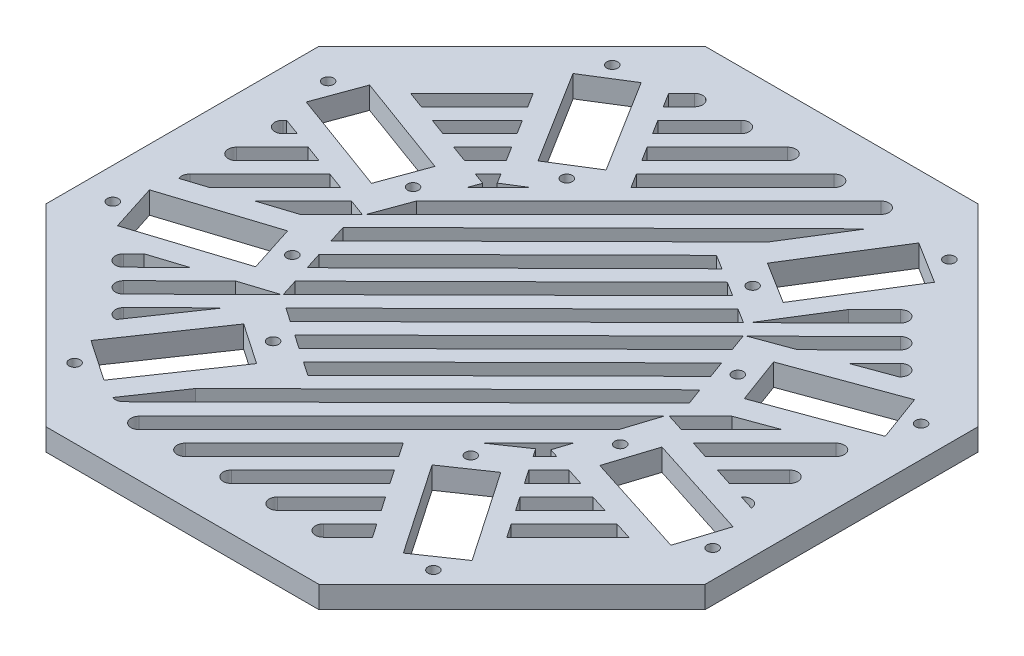
SolidWorks part; units mm, degrees
other "Camera1"
ref_plane "Front Plane" through (0, 0, 0) normal (0, 0, 1) x (1, 0, 0)
ref_plane "Top Plane" through (0, 0, 0) normal (0, 1, 0) x (1, 0, 0)
ref_plane "Right Plane" through (0, 0, 0) normal (1, 0, 0) x (0, 0, -1)
sketch "Sketch" plane through (0, 0, 0) normal (0, 1, 0) x (1, 0, 0)
  line L0 (0, 0) -> (60, 0) construction
  line L1 (0, 0) -> (60, 24.8528) construction
  line L2 (-6.8563, 54.06) -> (-15.6607, 52.1942)
  line L3 (60, 24.8528) -> (24.8528, 60)
  line L4 (24.8528, 60) -> (-24.8528, 60)
  line L5 (-24.8528, 60) -> (-60, 24.8528)
  line L6 (-60, 24.8528) -> (-60, -24.8528)
  line L7 (-60, -24.8528) -> (-24.8528, -60)
  line L8 (-24.8528, -60) -> (24.8528, -60)
  line L9 (24.8528, -60) -> (60, -24.8528)
  line L10 (60, -24.8528) -> (60, 24.8528)
  line L11 (50.7227, 19.9174) -> (46.7526, 27.9944)
  line L12 (46.7526, 27.9944) -> (41.5072, 35.3079)
  line L13 (41.5072, 35.3079) -> (35.1296, 41.6582)
  line L14 (35.1296, 41.6582) -> (27.7938, 46.8721)
  line L15 (27.7938, 46.8721) -> (19.6998, 50.8076)
  line L16 (19.6998, 50.8076) -> (11.0685, 53.3571)
  line L17 (11.0685, 53.3571) -> (2.1352, 54.4512)
  line L18 (2.1352, 54.4512) -> (-6.8563, 54.06)
  line L19 (-15.6607, 52.1942) -> (-24.038, 48.9047)
  line L20 (-24.038, 48.9047) -> (-31.7596, 44.2811)
  line L21 (-31.7596, 44.2811) -> (-38.6149, 38.4497)
  line L22 (-38.6149, 38.4497) -> (-44.4169, 31.5695)
  line L23 (-44.4169, 31.5695) -> (-49.0072, 23.8282)
  line L24 (-49.0072, 23.8282) -> (-52.2608, 15.4369)
  line L25 (-52.2608, 15.4369) -> (-54.0889, 6.6245)
  line L26 (-54.0889, 6.6245) -> (-54.4415, -2.3686)
  line L27 (-54.4415, -2.3686) -> (-53.3092, -11.2971)
  line L28 (-53.3092, -11.2971) -> (-50.7227, -19.9174)
  line L29 (-50.7227, -19.9174) -> (-46.7526, -27.9944)
  line L30 (-46.7526, -27.9944) -> (-41.5072, -35.3079)
  line L31 (-41.5072, -35.3079) -> (-35.1296, -41.6582)
  line L32 (-35.1296, -41.6582) -> (-27.7938, -46.8721)
  line L33 (-27.7938, -46.8721) -> (-19.6998, -50.8076)
  line L34 (-19.6998, -50.8076) -> (-11.0685, -53.3571)
  line L35 (-11.0685, -53.3571) -> (-2.1352, -54.4512)
  line L36 (-2.1352, -54.4512) -> (6.8563, -54.06)
  line L37 (6.8563, -54.06) -> (15.6607, -52.1942)
  line L38 (15.6607, -52.1942) -> (24.038, -48.9047)
  line L39 (24.038, -48.9047) -> (31.7596, -44.2811)
  line L40 (31.7596, -44.2811) -> (38.6149, -38.4497)
  line L41 (38.6149, -38.4497) -> (44.4169, -31.5695)
  line L42 (44.4169, -31.5695) -> (49.0072, -23.8282)
  line L43 (49.0072, -23.8282) -> (52.2608, -15.4369)
  line L44 (52.2608, -15.4369) -> (54.0889, -6.6245)
  line L45 (54.0889, -6.6245) -> (54.4415, 2.3686)
  line L46 (54.4415, 2.3686) -> (53.3092, 11.2971)
  line L47 (53.3092, 11.2971) -> (50.7227, 19.9174)
  line L48 (0.3388, 60) -> (0.3388, -60) construction
  line L49 (-24.9398, 48.451) -> (-32.5744, 43.6852)
  line L50 (-24.9398, 48.451) -> (-14.3492, 31.4852)
  line L51 (-32.5744, 43.6852) -> (-21.9838, 26.7194)
  line L52 (-14.3492, 31.4852) -> (-21.9838, 26.7194)
  line L53 (-49.2797, 23.3542) -> (-52.3773, 14.904)
  line L54 (-49.2797, 23.3542) -> (-30.5016, 16.4706)
  line L55 (-52.3773, 14.904) -> (-33.5992, 8.0205)
  line L56 (-30.5016, 16.4706) -> (-33.5992, 8.0205)
  line L57 (-52.7908, -13.2188) -> (-50.0451, -21.7898)
  line L58 (-52.7908, -13.2188) -> (-33.7443, -7.1172)
  line L59 (-50.0451, -21.7898) -> (-30.9986, -15.6881)
  line L60 (-33.7443, -7.1172) -> (-30.9986, -15.6881)
  line L61 (-34.3519, -42.3018) -> (-26.9207, -47.379)
  line L62 (-34.3519, -42.3018) -> (-23.0692, -25.7881)
  line L63 (-26.9207, -47.379) -> (-15.6381, -30.8653)
  line L64 (-23.0692, -25.7881) -> (-15.6381, -30.8653)
  line L65 (27.5983, -47.379) -> (16.3156, -30.8653)
  line L66 (23.7468, -25.7881) -> (16.3156, -30.8653)
  line L67 (35.0295, -42.3018) -> (23.7468, -25.7881)
  line L68 (35.0295, -42.3018) -> (27.5983, -47.379)
  line L69 (53.0549, 14.904) -> (34.2768, 8.0205)
  line L70 (31.1792, 16.4706) -> (34.2768, 8.0205)
  line L71 (49.9573, 23.3542) -> (31.1792, 16.4706)
  line L72 (49.9573, 23.3542) -> (53.0549, 14.904)
  line L73 (33.252, 43.6852) -> (22.6614, 26.7194)
  line L74 (15.0268, 31.4852) -> (22.6614, 26.7194)
  line L75 (25.6174, 48.451) -> (15.0268, 31.4852)
  line L76 (25.6174, 48.451) -> (33.252, 43.6852)
  line L77 (50.7227, -21.7898) -> (31.6761, -15.6881)
  line L78 (34.4219, -7.1172) -> (31.6761, -15.6881)
  line L79 (53.4684, -13.2188) -> (34.4219, -7.1172)
  line L80 (53.4684, -13.2188) -> (50.7227, -21.7898)
  line L81 (-30.5016, 16.4706) -> (-29.1249, 20.2263) construction
  line L82 (-29.1249, 20.2263) -> (-23.4915, 18.1612) construction
  line L83 (-33.5992, 8.0205) -> (-34.9759, 4.2649) construction
  line L84 (-34.9759, 4.2649) -> (-29.3425, 2.1998) construction
  line L85 (-52.3773, 14.904) -> (-53.754, 11.1484) construction
  line L86 (-53.754, 11.1484) -> (-59.3874, 13.2135) construction
  line L87 (-21.9838, 26.7194) -> (-25.377, 24.6013) construction
  line L88 (-25.377, 24.6013) -> (-22.1998, 19.5115) construction
  line L89 (-14.3492, 31.4852) -> (-10.9561, 33.6033) construction
  line L90 (-10.9561, 33.6033) -> (-7.7789, 28.5135) construction
  line L91 (-24.9398, 48.451) -> (-21.5467, 50.5691) construction
  line L92 (-21.5467, 50.5691) -> (-24.1943, 54.8106) construction
  line L93 (15.0268, 31.4852) -> (11.146, 33.9076) construction
  line L94 (11.146, 33.9076) -> (7.9689, 28.8179) construction
  line L95 (22.6614, 26.7194) -> (25.567, 24.9056) construction
  line L96 (25.567, 24.9056) -> (22.3898, 19.8159) construction
  line L97 (33.252, 43.6852) -> (36.1576, 41.8715) construction
  line L98 (36.1576, 41.8715) -> (38.8052, 46.1129) construction
  line L99 (31.1792, 16.4706) -> (29.8827, 20.0073) construction
  line L100 (29.8827, 20.0073) -> (24.2493, 17.9422) construction
  line L101 (34.2768, 8.0205) -> (35.7337, 4.0459) construction
  line L102 (35.7337, 4.0459) -> (30.1003, 1.9809) construction
  line L103 (53.0549, 14.904) -> (54.5118, 10.9295) construction
  line L104 (54.5118, 10.9295) -> (60.1453, 12.9945) construction
  line L105 (31.6761, -15.6881) -> (30.4558, -19.4974) construction
  line L106 (30.4558, -19.4974) -> (24.7419, -17.6669) construction
  line L107 (34.4219, -7.1172) -> (35.6422, -3.3079) construction
  line L108 (35.6422, -3.3079) -> (29.9283, -1.4774) construction
  line L109 (53.4684, -13.2188) -> (54.6887, -9.4095) construction
  line L110 (54.6887, -9.4095) -> (59.4504, -10.9349) construction
  line L111 (23.7468, -25.7881) -> (26.5876, -23.8472) construction
  line L112 (26.5876, -23.8472) -> (23.2028, -18.893) construction
  line L113 (16.3156, -30.8653) -> (12.551, -33.4374) construction
  line L114 (12.551, -33.4374) -> (9.1662, -28.4833) construction
  line L115 (27.5983, -47.379) -> (23.8336, -49.9511) construction
  line L116 (23.8336, -49.9511) -> (26.6543, -54.0795) construction
  line L117 (-23.0692, -25.7881) -> (-19.6844, -20.834) construction
  line L118 (-19.6844, -20.834) -> (-22.9872, -18.5774) construction
  line L119 (-15.6381, -30.8653) -> (-12.2533, -25.9112) construction
  line L120 (-12.2533, -25.9112) -> (-8.9506, -28.1677) construction
  line L121 (-34.3519, -42.3018) -> (-37.6546, -40.0452) construction
  line L122 (-37.6546, -40.0452) -> (-40.4753, -44.1736) construction
  line L123 (-52.7908, -13.2188) -> (-54.0112, -9.4095) construction
  line L124 (-54.0112, -9.4095) -> (-58.7728, -10.9349) construction
  line L125 (-33.7443, -7.1172) -> (-34.9647, -3.3079) construction
  line L126 (-34.9647, -3.3079) -> (-29.2507, -1.4774) construction
  line L127 (-30.9986, -15.6881) -> (-29.7783, -19.4974) construction
  line L128 (-29.7783, -19.4974) -> (-24.0643, -17.6669) construction
  line L129 (-24.1943, 54.8106) -> (-7.7789, 28.5135)
  line L130 (-24.1943, 54.8106) -> (-38.6153, 45.8086)
  line L131 (-7.7789, 28.5135) -> (-22.1998, 19.5115)
  line L132 (-38.6153, 45.8086) -> (-22.1998, 19.5115)
  line L133 (7.9689, 28.8179) -> (22.3898, 19.8159)
  line L134 (7.9689, 28.8179) -> (24.3843, 55.1149)
  line L135 (22.3898, 19.8159) -> (38.8052, 46.1129)
  line L136 (24.3843, 55.1149) -> (38.8052, 46.1129)
  line L137 (24.2493, 17.9422) -> (30.1003, 1.9809)
  line L138 (24.2493, 17.9422) -> (54.2942, 28.9559)
  line L139 (30.1003, 1.9809) -> (60.1453, 12.9945)
  line L140 (54.2942, 28.9559) -> (60.1453, 12.9945)
  line L141 (24.7419, -17.6669) -> (29.9283, -1.4774)
  line L142 (24.7419, -17.6669) -> (54.264, -27.1245)
  line L143 (29.9283, -1.4774) -> (59.4504, -10.9349)
  line L144 (54.264, -27.1245) -> (59.4504, -10.9349)
  line L145 (23.2028, -18.893) -> (9.1662, -28.4833)
  line L146 (23.2028, -18.893) -> (40.6909, -44.4892)
  line L147 (9.1662, -28.4833) -> (26.6543, -54.0795)
  line L148 (40.6909, -44.4892) -> (26.6543, -54.0795)
  line L149 (-40.4753, -44.1736) -> (-22.9872, -18.5774)
  line L150 (-40.4753, -44.1736) -> (-26.4387, -53.7639)
  line L151 (-22.9872, -18.5774) -> (-8.9506, -28.1677)
  line L152 (-26.4387, -53.7639) -> (-8.9506, -28.1677)
  line L153 (-58.7728, -10.9349) -> (-29.2507, -1.4774)
  line L154 (-58.7728, -10.9349) -> (-53.5864, -27.1245)
  line L155 (-29.2507, -1.4774) -> (-24.0643, -17.6669)
  line L156 (-53.5864, -27.1245) -> (-24.0643, -17.6669)
  line L157 (-59.3874, 13.2135) -> (-29.3425, 2.1998)
  line L158 (-59.3874, 13.2135) -> (-53.5364, 29.1749)
  line L159 (-29.3425, 2.1998) -> (-23.4915, 18.1612)
  line L160 (-53.5364, 29.1749) -> (-23.4915, 18.1612)
  line L161 (-32.0504, 12.2456) -> (-29.2337, 11.213) construction
  line L162 (-50.8285, 19.1291) -> (-53.6452, 20.1616) construction
  line L163 (-18.1665, 29.1023) -> (-16.5779, 26.5574) construction
  line L164 (-28.7571, 46.0681) -> (-30.3457, 48.613) construction
  line L165 (18.8441, 29.1023) -> (17.2555, 26.5574) construction
  line L166 (29.4347, 46.0681) -> (31.0233, 48.613) construction
  line L167 (32.728, 12.2456) -> (29.9113, 11.213) construction
  line L168 (51.5061, 19.1291) -> (54.3228, 20.1616) construction
  line L169 (52.0955, -17.5043) -> (54.9525, -18.4195) construction
  line L170 (33.049, -11.4026) -> (30.192, -10.4874) construction
  line L171 (31.3139, -44.8404) -> (33.0063, -47.3174) construction
  line L172 (20.0312, -28.3267) -> (18.3388, -25.8496) construction
  line L173 (-30.6363, -44.8404) -> (-32.3287, -47.3174) construction
  line L174 (-19.3537, -28.3267) -> (-17.6613, -25.8496) construction
  line L175 (-51.418, -17.5043) -> (-54.275, -18.4195) construction
  line L176 (-32.3715, -11.4026) -> (-29.5145, -10.4874) construction
  line L177 (24.8528, 60) -> (0, 0) construction
  line L178 (60, -24.8528) -> (0, 0) construction
  line L179 (0, 0) -> (24.8528, -60) construction
  line L180 (-24.8528, -60) -> (0, 0) construction
  line L181 (0, 0) -> (-60, -24.8528) construction
  line L182 (-60, 24.8528) -> (0, 0) construction
  line L183 (0, 0) -> (-24.8528, 60) construction
  line L184 (-19.8494, 50.5494) -> (20.2308, 50.5494) construction
  line L185 (20.2308, 50.5494) -> (50.7227, 19.9174) construction
  line L186 (50.7227, -21.7898) -> (50.7227, 19.9174) construction
  line L187 (50.7227, -21.7898) -> (19.8494, -50.5494) construction
  line L188 (19.8494, -50.5494) -> (-20.2308, -50.5494) construction
  line L189 (-20.2308, -50.5494) -> (-50.7227, -19.9174) construction
  line L190 (-50.7227, -19.9174) -> (-50.1861, 20.7878) construction
  line L191 (-50.1861, 20.7878) -> (-19.8494, 50.5494) construction
  line L192 (-35.5159, -35.194) -> (35.5159, 35.194) construction
  line L193 (-36.5718, -34.1285) -> (34.4601, 36.2595)
  line L194 (-34.4601, -36.2595) -> (36.5718, 34.1285)
  line L195 (-31.2733, -39.4367) -> (39.7586, 30.9514) construction
  line L196 (-32.3291, -38.3712) -> (38.7028, 32.0169)
  line L197 (-30.2175, -40.5021) -> (40.8144, 29.8859)
  line L198 (-27.0306, -43.6793) -> (44.0012, 26.7087) construction
  line L199 (-28.0865, -42.6138) -> (42.9454, 27.7742)
  line L200 (-25.9748, -44.7448) -> (45.057, 25.6433)
  line L201 (-22.788, -47.9219) -> (48.2439, 22.4661) construction
  line L202 (-23.8438, -46.8565) -> (47.188, 23.5316)
  line L203 (-21.7322, -48.9874) -> (49.2997, 21.4006)
  line L204 (-39.7586, -30.9514) -> (31.2733, 39.4367) construction
  line L205 (-40.8144, -29.8859) -> (30.2175, 40.5021)
  line L206 (-38.7028, -32.0169) -> (32.3291, 38.3712)
  line L207 (-44.0012, -26.7087) -> (27.0306, 43.6793) construction
  line L208 (-45.057, -25.6433) -> (25.9748, 44.7448)
  line L209 (-42.9454, -27.7742) -> (28.0865, 42.6138)
  line L210 (-48.2439, -22.4661) -> (22.788, 47.9219) construction
  line L211 (-49.2997, -21.4006) -> (21.7322, 48.9874)
  line L212 (-47.188, -23.5316) -> (23.8438, 46.8565)
  line L213 (-16.9781, -50.9084) -> (50.7227, 16.7923) construction
  line L216 (0, 0) -> (38.2978, -38.7195) construction
  line L217 (0, 0) -> (4.2193, -4.2658) construction
  line L218 (4.2193, -4.2658) -> (8.4387, -8.5316) construction
  line L219 (8.4387, -8.5316) -> (12.658, -12.7974) construction
  line L220 (12.658, -12.7974) -> (16.8723, -17.0581) construction
  line L221 (16.8723, -17.0581) -> (21.0967, -21.329) construction
  line L222 (21.0967, -21.329) -> (25.3161, -25.5948) construction
  line L223 (25.3161, -25.5948) -> (29.5354, -29.8606) construction
  line L224 (29.5354, -29.8606) -> (33.7548, -34.1264) construction
  line L225 (-18.036, -49.8506) -> (49.6648, 17.8502)
  line L226 (-15.9202, -51.9663) -> (51.7805, 15.7344)
  line L227 (-8.5292, -50.9549) -> (50.7227, 8.2969) construction
  line L228 (-9.5899, -49.8943) -> (49.662, 9.3576)
  line L229 (-7.4685, -52.0156) -> (51.7833, 7.2362)
  line L230 (-0.0905, -51.0014) -> (50.7227, -0.1882) construction
  line L231 (-1.1512, -49.9407) -> (49.662, 0.8724)
  line L232 (0.9702, -52.0621) -> (51.7833, -1.2489)
  line L233 (8.3482, -51.0479) -> (50.7227, -8.6734) construction
  line L234 (7.2875, -49.9872) -> (49.662, -7.6127)
  line L235 (9.4089, -52.1085) -> (51.7833, -9.7341)
  line L236 (16.7869, -51.0943) -> (50.7227, -17.1585) construction
  line L237 (15.7262, -50.0337) -> (49.662, -16.0979)
  line L238 (17.8475, -52.155) -> (51.7833, -18.2192)
  line L239 (0, 0) -> (-38.5256, 38.5256) construction
  line L240 (0, 0) -> (-4.2426, 4.2426) construction
  line L241 (-4.2426, 4.2426) -> (-8.4853, 8.4853) construction
  line L242 (-8.4853, 8.4853) -> (-12.7279, 12.7279) construction
  line L243 (-12.7279, 12.7279) -> (-16.9706, 16.9706) construction
  line L244 (-12.7279, 12.7279) -> (-16.9706, 16.9706) construction
  line L245 (-50.5494, -16.6083) -> (16.6083, 50.5494) construction
  line L246 (-51.6101, -15.5476) -> (15.5476, 51.6101)
  line L247 (-49.4888, -17.669) -> (17.669, 49.4888)
  line L248 (-16.9706, 16.9706) -> (-21.2132, 21.2132) construction
  line L249 (-50.5494, -8.123) -> (8.123, 50.5494) construction
  line L250 (-51.6101, -7.0624) -> (7.0624, 51.6101)
  line L251 (-49.4888, -9.1837) -> (9.1837, 49.4888)
  line L252 (-21.2132, 21.2132) -> (-25.4558, 25.4558) construction
  line L253 (-50.5494, 0.3623) -> (-0.3623, 50.5494) construction
  line L254 (-51.6101, 1.4229) -> (-1.4229, 51.6101)
  line L255 (-49.4888, -0.6984) -> (0.6984, 49.4888)
  line L256 (-25.4558, 25.4558) -> (-29.6985, 29.6985) construction
  line L257 (-50.5494, 8.8476) -> (-8.8476, 50.5494) construction
  line L258 (-51.6101, 9.9082) -> (-9.9082, 51.6101)
  line L259 (-49.4888, 7.7869) -> (-7.7869, 49.4888)
  line L260 (-29.6985, 29.6985) -> (-33.9411, 33.9411) construction
  line L261 (-50.5494, 17.3328) -> (-17.3328, 50.5494) construction
  line L262 (-51.6101, 18.3935) -> (-18.3935, 51.6101)
  line L263 (-49.4888, 16.2722) -> (-16.2722, 49.4888)
  circle A0 centre (0, 0) radius 60 construction
  circle A1 centre (0, 0) radius 54.3069 construction
  circle A2 centre (-54.275, -18.4195) radius 1
  circle A3 centre (-29.5145, -10.4874) radius 1
  circle A4 centre (-29.2337, 11.213) radius 1
  circle A5 centre (-53.6452, 20.1616) radius 1
  circle A6 centre (-30.3457, 48.613) radius 1
  circle A7 centre (-16.5779, 26.5574) radius 1
  circle A8 centre (31.0233, 48.613) radius 1
  circle A9 centre (17.2555, 26.5574) radius 1
  circle A10 centre (54.3228, 20.1616) radius 1
  circle A11 centre (29.9113, 11.213) radius 1
  circle A12 centre (54.9525, -18.4195) radius 1
  circle A13 centre (30.192, -10.4874) radius 1
  circle A14 centre (33.0063, -47.3174) radius 1
  circle A15 centre (18.3388, -25.8496) radius 1
  circle A16 centre (-17.6613, -25.8496) radius 1
  circle A17 centre (-32.3287, -47.3174) radius 1
  arc A18 (-36.5718, -34.1285) -> (-34.4601, -36.2595) centre (-35.5159, -35.194) ccw
  arc A19 (36.5718, 34.1285) -> (34.4601, 36.2595) centre (35.5159, 35.194) ccw
  arc A20 (-32.3291, -38.3712) -> (-30.2175, -40.5021) centre (-31.2733, -39.4367) ccw
  arc A21 (40.8144, 29.8859) -> (38.7028, 32.0169) centre (39.7586, 30.9514) ccw
  arc A22 (-28.0865, -42.6138) -> (-25.9748, -44.7448) centre (-27.0306, -43.6793) ccw
  arc A23 (45.057, 25.6433) -> (42.9454, 27.7742) centre (44.0012, 26.7087) ccw
  arc A24 (-23.8438, -46.8565) -> (-21.7322, -48.9874) centre (-22.788, -47.9219) ccw
  arc A25 (49.2997, 21.4006) -> (47.188, 23.5316) centre (48.2439, 22.4661) ccw
  arc A26 (-40.8144, -29.8859) -> (-38.7028, -32.0169) centre (-39.7586, -30.9514) ccw
  arc A27 (32.3291, 38.3712) -> (30.2175, 40.5021) centre (31.2733, 39.4367) ccw
  arc A28 (-45.057, -25.6433) -> (-42.9454, -27.7742) centre (-44.0012, -26.7087) ccw
  arc A29 (28.0865, 42.6138) -> (25.9748, 44.7448) centre (27.0306, 43.6793) ccw
  arc A30 (-49.2997, -21.4006) -> (-47.188, -23.5316) centre (-48.2439, -22.4661) ccw
  arc A31 (23.8438, 46.8565) -> (21.7322, 48.9874) centre (22.788, 47.9219) ccw
  arc A34 (-18.036, -49.8506) -> (-15.9202, -51.9663) centre (-16.9781, -50.9084) ccw
  arc A35 (51.7805, 15.7344) -> (49.6648, 17.8502) centre (50.7227, 16.7923) ccw
  arc A36 (-9.5899, -49.8943) -> (-7.4685, -52.0156) centre (-8.5292, -50.9549) ccw
  arc A37 (51.7833, 7.2362) -> (49.662, 9.3576) centre (50.7227, 8.2969) ccw
  arc A38 (-1.1512, -49.9407) -> (0.9702, -52.0621) centre (-0.0905, -51.0014) ccw
  arc A39 (51.7833, -1.2489) -> (49.662, 0.8724) centre (50.7227, -0.1882) ccw
  arc A40 (7.2875, -49.9872) -> (9.4089, -52.1085) centre (8.3482, -51.0479) ccw
  arc A41 (51.7833, -9.7341) -> (49.662, -7.6127) centre (50.7227, -8.6734) ccw
  arc A42 (15.7262, -50.0337) -> (17.8475, -52.155) centre (16.7869, -51.0943) ccw
  arc A43 (51.7833, -18.2192) -> (49.662, -16.0979) centre (50.7227, -17.1585) ccw
  arc A44 (-51.6101, -15.5476) -> (-49.4888, -17.669) centre (-50.5494, -16.6083) ccw
  arc A45 (17.669, 49.4888) -> (15.5476, 51.6101) centre (16.6083, 50.5494) ccw
  arc A46 (-51.6101, -7.0624) -> (-49.4888, -9.1837) centre (-50.5494, -8.123) ccw
  arc A47 (9.1837, 49.4888) -> (7.0624, 51.6101) centre (8.123, 50.5494) ccw
  arc A48 (-51.6101, 1.4229) -> (-49.4888, -0.6984) centre (-50.5494, 0.3623) ccw
  arc A49 (0.6984, 49.4888) -> (-1.4229, 51.6101) centre (-0.3623, 50.5494) ccw
  arc A50 (-51.6101, 9.9082) -> (-49.4888, 7.7869) centre (-50.5494, 8.8476) ccw
  arc A51 (-7.7869, 49.4888) -> (-9.9082, 51.6101) centre (-8.8476, 50.5494) ccw
  arc A52 (-51.6101, 18.3935) -> (-49.4888, 16.2722) centre (-50.5494, 17.3328) ccw
  arc A53 (-16.2722, 49.4888) -> (-18.3935, 51.6101) centre (-17.3328, 50.5494) ccw
  point P196 (0, 0)
  point P205 (4.2426, -4.2426)
  point P212 (8.4853, -8.4853)
  point P219 (12.7279, -12.7279)
  point P225 (-4.2426, 4.2426)
  point P232 (-8.4853, 8.4853)
  point P239 (-12.7279, 12.7279)
  point P245 (16.8723, -17.0581)
  point P260 (21.0967, -21.329)
  point P268 (25.3161, -25.5948)
  point P275 (29.5354, -29.8606)
  point P281 (33.7548, -34.1264)
  point P294 (-16.9706, 16.9706)
  point P302 (-21.2132, 21.2132)
  point P310 (-25.4558, 25.4558)
  point P318 (-29.6985, 29.6985)
  point P326 (-33.9411, 33.9411)
  dimension "D5" = 4
  dimension "D7" = 9
  dimension "D1" = 9
  dimension "D2" = 20
  dimension "D3" = 20
  dimension "D4" = 20
  dimension "D8" = 9
  dimension "D9" = 9
  dimension "D10" = 9
  dimension "D11" = 20
  dimension "D6" = 4
extrude "Boss-Extrude1" add sketch "Sketch" along normal blind 4 contours A53 L19 L2 L18 L17 L16 A45 L15 L134 L136 L3 L4 L5 L6 L7 L8 L9 L148 L147 L38 L238 A42 L37 L36 L35 L34 L226 A34 L33 A24 L152 L150 L149 L31 L30 L29 L156 L154 L153 L27 L26 L25 L157 L158 L160 L23 L22 L21 | L138 L140 L10 L3 L135 L13 L12 L11 | A25 L71 L72 L69 L47 L46 L139 L10 L140 L138 L11 A10 | A31 L15 L75 L76 L73 L14 L13 L135 L3 L136 L134 A8 | L40 L146 L9 L10 L139 L46 L45 L44 L143 L144 L142 L42 L41 | A43 L80 L77 L43 L42 L142 L144 L143 L44 L79 A12 | L148 L9 L146 L40 L67 L68 L65 L39 L38 L147 A14 | A24 L33 L63 L61 L32 L62 L31 L149 L150 L152 A17 | A44 L57 L58 L28 L27 L153 L154 L156 L29 A30 L59 A2 | A52 L262 L53 L54 L24 L23 L160 L158 L157 L25 L55 A5 | L130 L132 L21 L51 L49 L20 L50 L19 L129 A6 | A20 L196 L62 L64 L151 L194 A18 L149 L31 L32 | L196 A20 L62 | L149 A18 L194 L151 L193 | L149 L193 L151 | L64 L197 L151 L196 A16 | L64 L199 L151 L197 | L63 L200 L151 L199 L64 | A24 L202 L152 L151 L200 L63 L33 | L202 A24 L33 L152 | L33 A24 L152 | L61 L32 L33 | L156 L206 L155 L205 | L209 L156 L205 L155 | L206 L156 L155 | A30 L29 L156 L208 L59 L212 | A3 L208 L60 L59 L156 L209 L155 | L59 A30 L29 L212 | A3 L208 L155 L212 L60 | L60 L212 L155 L211 L58 | L247 L58 L211 L155 L153 | L58 L247 L153 L246 | A46 L153 L27 L28 L58 L246 L251 | L57 A44 L28 | L29 A30 | A30 L59 L29 | A44 L28 L29 L57 | L28 A44 L57 | L153 A46 L251 | A50 L258 L157 L25 L26 L27 L153 A46 L250 L255 A48 L254 L259 | A4 L251 L157 L246 L159 | L157 L247 L159 L246 | L247 L157 L159 | L251 L153 L246 L157 | A4 L251 L159 L160 L250 L56 L55 L157 | L255 L54 L56 L250 L160 | L259 L54 L254 L160 | L54 L255 L160 L254 | L263 L54 L258 L160 | L54 L262 L160 L23 L24 | L54 L263 L160 L262 | L54 L259 L160 L258 | L157 L258 L55 L25 | L157 L259 L55 L258 | L259 L157 L254 L55 | L157 L255 L55 L254 | L255 L157 L250 L55 | L262 A52 L24 L53 | A52 L24 L25 L53 | L24 A52 L53 | L160 L262 L132 L21 L22 L23 | L263 L160 L258 L132 | L259 L160 L254 L132 | L255 L160 L250 L132 | A7 L250 L129 L255 L50 L52 L51 L132 | A7 L250 L132 L131 L251 L129 | L251 L131 L129 | L132 L255 L51 L254 | L259 L132 L254 L51 | L132 L259 L51 L258 | L263 L132 L258 L51 | L132 L263 L51 L262 | L50 L255 L129 L254 | L50 L259 L129 L258 | L263 L50 L258 L129 | L50 L263 L129 L262 | L50 L262 L129 L19 L20 | L132 L262 L51 L21 | L49 L20 L21 | L129 L262 L19 | A53 L263 L129 L258 A51 L259 L254 A49 L255 L250 A47 L251 L131 L159 L246 A45 L16 L17 L18 L2 L19 | L259 L50 L254 L129 | A45 L247 L159 L157 L153 L155 L211 L134 L15 L16 | A31 L15 L134 L211 | L212 A31 L15 L211 L134 | L15 A31 | A31 L212 L134 L133 L208 L75 L15 | L133 L209 L74 L75 L208 | A27 L206 L73 L74 L133 L193 L135 L13 L14 | L206 A27 L73 | A9 L205 L133 L206 L74 | A9 L205 L74 L209 L133 | L133 L194 L135 L193 | L194 L133 L135 | A23 L200 L138 L11 L12 L13 L135 L193 A19 L194 L133 L151 L196 L137 A21 L197 L199 | A25 L11 L138 L200 L71 L202 | L71 A25 L11 | L11 A25 L202 L71 | L71 L200 L138 L199 | L137 L199 L70 L71 L138 L197 | L137 L197 L138 L196 | L137 L196 L138 | A11 L200 L70 L199 L137 | A11 L200 L137 L202 L70 | L137 L203 L69 L70 L202 | L139 L225 L69 L203 L137 | L139 L226 L69 L225 | A37 L139 L46 L47 L69 L226 L228 | A41 L143 L44 L45 L46 L139 A37 L229 L231 A39 L232 L234 | L143 L228 L139 L226 | A34 L225 L141 L143 L139 L137 L203 A24 L33 L34 | L141 L225 L143 | L141 L226 L143 L225 | A13 L228 L143 L226 L141 | A13 L228 L141 L142 L229 L78 L79 L143 | L79 L231 L143 L229 | L79 L234 L143 L232 | L79 L232 L143 L231 | L235 A41 L143 L234 L79 | A41 L235 L79 L44 L143 | L142 L231 L77 L78 L229 | L142 L232 L77 L231 | L142 L234 L77 L232 | L142 L235 L77 L234 | L142 L237 L77 L235 | L142 L238 L77 L237 | L238 L142 L42 L43 L77 | L80 A43 | L238 L146 L40 L41 L42 L142 | L146 L237 L142 L235 | L146 L234 L142 L232 | L146 L231 L142 L229 | A42 L237 L147 L235 A40 L234 L232 A38 L231 L229 A36 L228 L145 L141 L226 L34 L35 L36 L37 L38 | L238 L67 L40 L146 | L67 L238 L146 L237 | L67 L237 L146 L235 | L67 L235 L146 L234 | L67 L234 L146 L232 | L67 L232 L146 L231 L66 | A15 L229 L147 L231 L65 L66 L146 | A15 L229 L146 L145 L228 L147 | L147 L228 L145 | L147 L232 L65 L231 | L147 L234 L65 L232 | L147 L235 L65 L234 | L147 L237 L65 L235 | L147 L238 L65 L237 | L238 L147 L38 L39 L65 | L152 L202 L137 L200 L151 | L151 L199 L137 L197 | A28 L208 L156 L29 L30 L31 L149 A18 L193 L151 L133 L206 L155 A26 L205 L209 | L209 L155 L205 L133 | L212 L155 L208 L133 L134 region at (-5.2382, 0, -41.4385) region at (-11.5819, 0, -54.6531) region at (-20.3787, 0, -50.0306) region at (-22.8906, 0, -48.3651) region at (-22.7016, 0, -49.6682) region at (-21.3712, 0, -46.5111) region at (-19.7406, 0, -43.899) region at (-5.4906, 0, -24.2149) region at (-18.1101, 0, -41.2869) region at (-29.9055, 0, -8.4517) region at (-29.5739, 0, -4.9925) region at (-32.8662, 0, -40.3303) region at (-30.8064, 0, -37.0759) region at (-16.4795, 0, -38.6748) region at (-29.1758, 0, -34.4638) region at (22.998, 0, -52.4701) region at (20.7639, 0, -48.5368) region at (-29.3566, 0, -2.3707) region at (-30.5462, 0, -11.841) region at (-39.5032, 0, 1.2124) region at (-30.7451, 0, -44.8563) region at (-39.9238, 0, -33.2884) region at (-14.849, 0, -36.0627) region at (-27.5453, 0, -31.8517) region at (-35.1365, 0, -28.5614) region at (23.3773, 0, -49.1339) region at (19.1678, 0, -43.9493) region at (-11.8525, 0, -27.1151) region at (-20.4337, 0, -20.8478) region at (-48.5565, 0, 9.6241) region at (-41.4157, 0, 7.4746) region at (-46.9256, 0, -24.7771) region at (-44.2439, 0, -23.6383) region at (-18.0743, 0, -28.3287) region at (-25.9147, 0, -29.2396) region at (-41.1393, 0, -22.5003) region at (16.0364, 0, -37.1421) region at (-9.1996, 0, -12.0374) region at (-35.29, 0, 5.5075) region at (-31.2395, 0, 5.5499) region at (-29.0947, 0, -17.2782) region at (-25.7289, 0, -21.1107) region at (-45.4151, 0, 0.5065) region at (-38.8528, 0, -7.8162) region at (-50.0171, 0, 8.6736) region at (-48.298, 0, -25.4541) region at (-24.2842, 0, -26.6275) region at (-30.4173, 0, -24.8238) region at (-38.0347, 0, -21.3622) region at (-30.1011, 0, 8.6064) region at (47.8139, 0, -32.8222) region at (-31.8256, 0, -19.0861) region at (-41.9574, 0, -8.9543) region at (-52.8278, 0, 13.0119) region at (-34.9302, 0, -20.2242) region at (13.4874, 0, -30.6011) region at (-33.6957, 0, 16.5549) region at (26.8751, 0, -31.4168) region at (18.1071, 0, -12.7508) region at (-45.062, 0, -10.0923)
extrude "Boss-Extrude2" add sketch "Sketch<10>" along normal blind 4 contours L238 L38 L147 region at (21.6028, 0, 49.233)
sketch "Sketch<10>" plane through (0, 0, 0) normal (0, 1, 0) x (1, 0, 0) same geometry as "Sketch"
